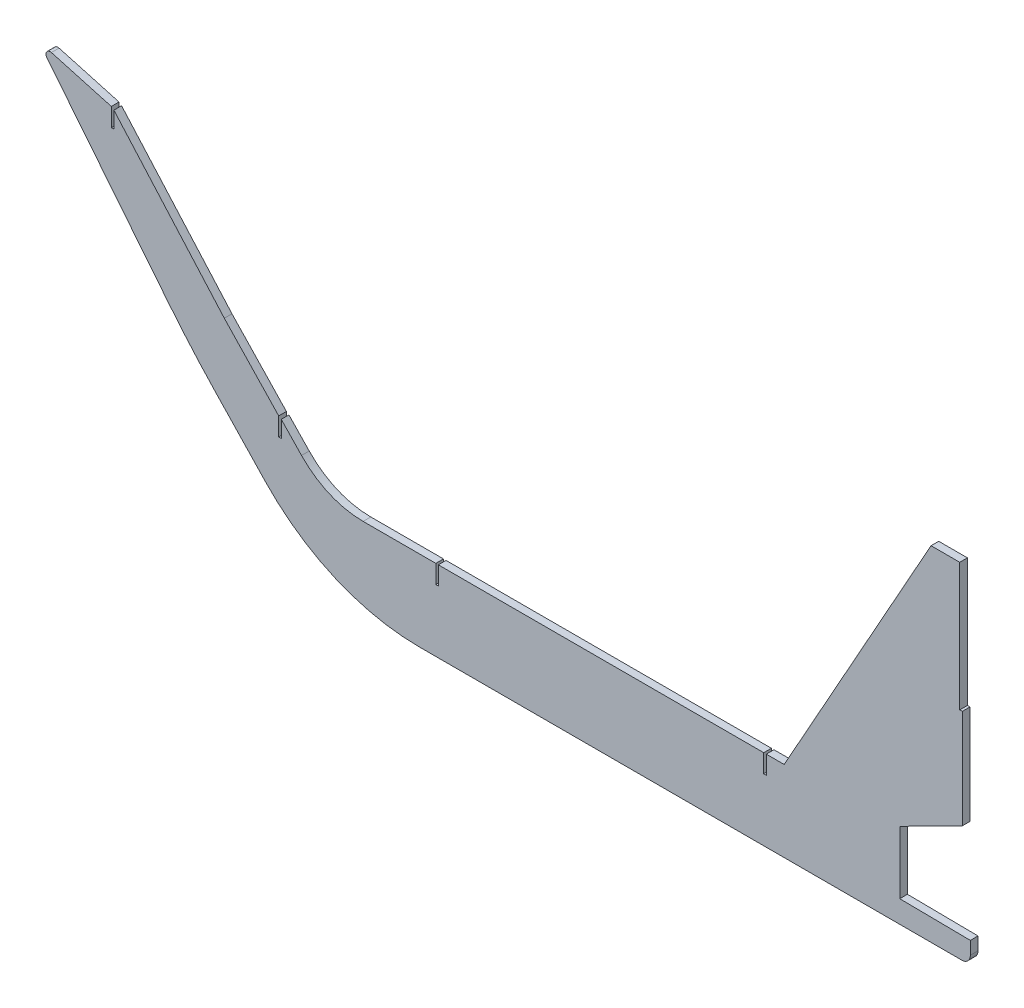
SolidWorks part; units mm, degrees
ref_plane "Plan de face" through (0, 0, 0) normal (0, 0, 1) x (1, 0, 0)
ref_plane "Plan de dessus" through (0, 0, 0) normal (0, 1, 0) x (1, 0, 0)
ref_plane "Plan de droite" through (0, 0, 0) normal (1, 0, 0) x (0, 0, -1)
sketch "Esquisse2" plane through (0, 0, 0) normal (0, 0, 1) x (1, 0, 0)
  line L0 (0, 0) -> (-753.5145, 0)
  line L4 (-9.4344, 136.7799) -> (-82.8018, 99.6206)
  line L5 (-82.8018, 99.6206) -> (-82.8018, 26.0593)
  line L6 (-82.8018, 26.0593) -> (0, 25.1181)
  line L7 (0, 25.1181) -> (0, 0)
  line L8 (-875.399, 219.6167) -> (-811.5708, 152.3034)
  line L9 (-755.2746, 94.6399) -> (-627.232, 94.6399)
  line L10 (-218.4491, 94.6399) -> (-46.0933, 403.1399)
  line L11 (-46.0933, 403.1399) -> (-12.4344, 403.1399)
  line L13 (-753.5145, 0) -> (-915.1902, 170.5035)
  line L14 (-915.1902, 170.5035) -> (-1093.2835, 392.3872)
  line L15 (-1093.2835, 392.3872) -> (-1007.9829, 368.609)
  line L16 (-1007.9829, 368.609) -> (-1007.9829, 347.109)
  line L17 (-1007.9829, 347.109) -> (-1004.9829, 347.109)
  line L18 (-1004.9829, 347.109) -> (-1004.9829, 366.3435)
  line L19 (-1004.9829, 366.3435) -> (-875.399, 219.6167)
  line L20 (-811.5708, 152.3034) -> (-811.5708, 130.8034)
  line L21 (-811.5708, 130.8034) -> (-808.5708, 130.8034)
  line L22 (-808.5708, 130.8034) -> (-808.5708, 150.3758)
  line L23 (-808.5708, 150.3758) -> (-755.2746, 94.6399)
  line L24 (-627.232, 94.6399) -> (-627.232, 73.1399)
  line L25 (-627.232, 73.1399) -> (-624.232, 73.1399)
  line L26 (-624.232, 73.1399) -> (-624.232, 94.6399)
  line L27 (-624.232, 94.6399) -> (-242.4448, 94.6399)
  line L28 (-242.4448, 94.6399) -> (-242.4448, 73.1399)
  line L29 (-242.4448, 73.1399) -> (-239.4448, 73.1399)
  line L30 (-239.4448, 73.1399) -> (-239.4448, 94.6399)
  line L31 (-239.4448, 94.6399) -> (-218.4491, 94.6399)
  line L33 (-12.4344, 253.1399) -> (-12.4344, 403.1399)
  line L34 (-9.4344, 136.7799) -> (-9.4344, 253.1399)
  line L35 (-9.4344, 253.1399) -> (-12.4344, 253.1399)
  point P4 (-1032.509, 243.1363)
  point P32 (-963.9935, 193.5556)
  point P34 (0, 0)
  point P35 (-1253.374, 247.8231)
  point P36 (0, 0)
  point P37 (0, 0)
  point P38 (0, 0)
  point P39 (-36.7946, 94.9485)
  point P40 (-36.7946, 114.6824)
  point P41 (-1314.1713, 400)
  point P42 (-1039.4398, 305.2274)
  point P43 (-1039.4398, 330.9304)
  point P44 (-1033.1211, 330.9304)
  point P45 (-917.3362, 260.5172)
  point P46 (-1156.1621, 362.3262)
  point P47 (-1127.0917, 355.0586)
  point P48 (-1127.0917, 288.7847)
  point P49 (-1156.1621, 325.1949)
  point P50 (-1127.0917, 325.1949)
  point P51 (-984.7321, 227.0539)
  point P52 (-1063.0593, 227.0539)
  point P53 (-970.2976, 227.0539)
  point P54 (0, 0)
  point P55 (0, 0)
  point P56 (0, 0)
  point P57 (0, 0)
  point P58 (-9.179, 265.7306)
  point P59 (-224.9067, 84.544)
  point P60 (-1156.1621, 388.5348)
  point P61 (-768.5316, 84.7741)
  point P62 (-1071.26, 340.9838)
  point P63 (-10.5247, 173.5062)
  point P64 (-9.9856, 171.0682)
  point P65 (-1066.1409, 340.3413)
  point P66 (-82.8018, 99.6206)
  point P67 (-1161.2757, 357.8869)
  point P68 (-941.9866, 182.2592)
  point P69 (0, 0)
  point P70 (-995.828, 339.7832)
  point P71 (-1118.8362, 366.7477)
  point P72 (-995.6467, 340.4124)
  point P73 (-1002.4542, 382.0485)
  point P74 (-995.1401, 382.5231)
  point P75 (-991.5881, 363.5149)
  point P76 (-996.6185, 366.2739)
  point P77 (-898.1286, 251.0494)
  point P78 (-1009.904, 368.609)
  point P79 (-1004.5896, 366.1289)
  point P80 (-1097.2114, 381.9703)
  point P81 (-1004.9829, 366.3435)
  point P82 (-1093.2835, 392.3872)
  point P83 (-875.399, 219.6167)
  point P84 (0, 0)
  point P85 (0, 0)
  dimension "D1" = 3
  dimension "D2" = 21.5
  dimension "D3" = 3
  dimension "D4" = 21.5
  dimension "D5" = 21.5
  dimension "D6" = 3
  dimension "D7" = 21.5
  dimension "D8" = 3
  dimension "D9" = 3
  dimension "D10" = 150
  dimension "D11" = 330
extrude "Boss.-Extru.1" add sketch "Esquisse2" along normal blind 9
fillet "Congé1" radius 1000 1 edges at (-915.1902, 170.5035, 4.5)
fillet "Congé2" radius 250 1 edges at (-753.5145, 0, 4.5)
fillet "Congé4" radius 10 1 edges at (0, 0, 4.5)
fillet "Congé5" radius 5 1 edges at (-1093.2835, 392.3872, 4.5)
fillet "Congé6" radius 100 1 edges at (-755.2746, 94.6399, 4.5)
